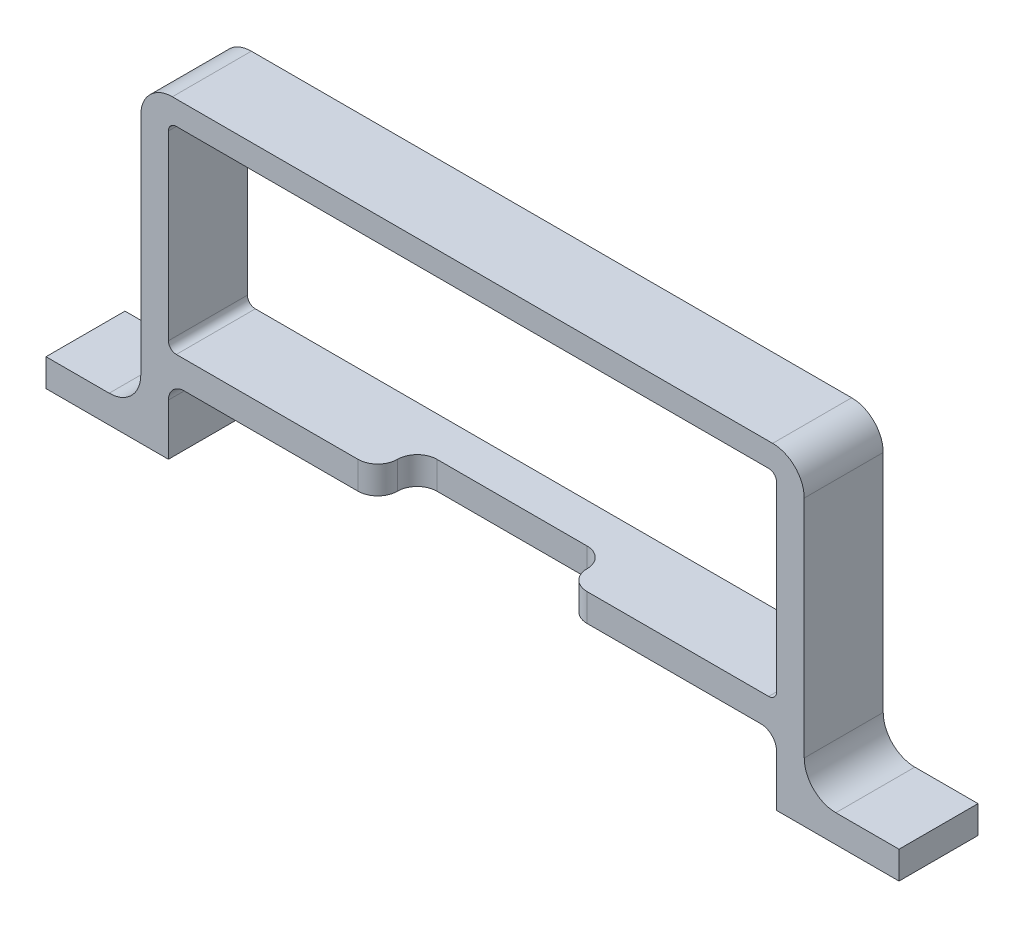
SolidWorks part; units mm, degrees
ref_plane "Alzado" through (0, 0, 0) normal (0, 0, 1) x (1, 0, 0)
ref_plane "Planta" through (0, 0, 0) normal (0, 1, 0) x (1, 0, 0)
ref_plane "Vista lateral" through (0, 0, 0) normal (1, 0, 0) x (0, 0, -1)
sketch "Croquis1" plane through (0, 0, 0) normal (0, 0, 1) x (1, 0, 0)
  line L2 (-39.6872, 1.2544) -> (-39.6872, 24.2544)
  line L7 (-43.1872, -3.2456) -> (-43.1872, 24.2544)
  line L8 (-38.6872, 25.2544) -> (-1.1872, 25.2544)
  line L10 (-43.1872, -4.2456) -> (-43.1872, -3.2456)
  line L13 (-39.6872, -5.2456) -> (-39.6872, -11.7456)
  line L15 (-39.6872, -11.7456) -> (-43.1872, -11.7456)
  line L17 (-43.1872, -11.7456) -> (-55.1872, -11.7456)
  line L21 (-43.1872, -11.7456) -> (-43.1872, -8.2456)
  line L22 (-47.1872, -8.2456) -> (-55.1872, -8.2456)
  line L23 (-55.1872, -11.7456) -> (-55.1872, -8.2456)
  line L24 (-1.1872, 25.2544) -> (-1.1872, 28.2544)
  line L25 (-1.1872, 28.2544) -> (-39.1872, 28.2544)
  line L26 (-37.6872, -3.2456) -> (-1.1872, -3.2456)
  line L27 (-1.1872, -3.2456) -> (-1.1872, 0.2544)
  line L28 (-1.1872, 0.2544) -> (-38.6872, 0.2544)
  arc A0 (-43.1872, 24.2544) -> (-39.1872, 28.2544) centre (-39.1872, 24.2544) cw
  arc A2 (-39.6872, 1.2544) -> (-38.6872, 0.2544) centre (-38.6872, 1.2544) ccw
  arc A3 (-39.6872, 24.2544) -> (-38.6872, 25.2544) centre (-38.6872, 24.2544) cw
  arc A5 (-39.6872, -5.2456) -> (-37.6872, -3.2456) centre (-37.6872, -5.2456) cw
  arc A10 (-43.1872, -4.2456) -> (-47.1872, -8.2456) centre (-47.1872, -4.2456) cw
  point P0 (-1.1872, 12.7544)
  dimension "D3" = 3.5
  dimension "D7" = 4
  dimension "D9" = 12.7544
  dimension "D5" = 2
  dimension "D6" = 37.5
  dimension "D4" = 4
  dimension "D17" = 1
  dimension "D2" = 3
  dimension "D8" = 37.5
  dimension "D10" = 3.5
  dimension "D11" = 6.5
  dimension "D12" = 8
  dimension "D13" = 12
  dimension "D14" = 3.5
  dimension "D15" = 36.5
  dimension "D16" = 23
extrude "Saliente-Extruir2" add sketch "Croquis1" along normal blind 10 contours L10 A10 L22 L23 L17 L15 L13 A5 L26 L27 L28 A2 L2 A3 L8 L24 L25 A0 L7 region at (-39.8695, 0.0721, 0)
mirror "Simetría2" about plane through (-1.1872, 0, 10) normal (-1, 0, 0) of "Saliente-Extruir2"
sketch "Croquis9" plane through (0, 0, 10) normal (0, 0, 1) x (1, 0, 0)
  line L0 (-37.6872, -3.2456) -> (35.3128, -3.2456) construction
  line L1 (10.8128, -6.7456) -> (-13.1872, -6.7456)
  line L2 (10.8128, -6.7456) -> (10.8128, 0.2544)
  line L3 (10.8128, 0.2544) -> (-13.1872, 0.2544)
  line L4 (-13.1872, -6.7456) -> (-13.1872, 0.2544)
  line L5 (10.8128, -6.7456) -> (-13.1872, 0.2544) construction
  line L6 (10.8128, 0.2544) -> (-13.1872, -6.7456) construction
  line L7 (36.3128, 0.2544) -> (-38.6872, 0.2544) construction
  point P0 (-1.1872, -3.2456)
  dimension "D1" = 24
extrude "Cortar-Extruir2" cut sketch "Croquis9" against normal blind 5
fillet "Redondeo3" radius 2.5 4 edges at (10.8128, -1.4956, 10) (10.8128, -1.4956, 5) (-13.1872, -1.4956, 5) (-13.1872, -1.4956, 10)
